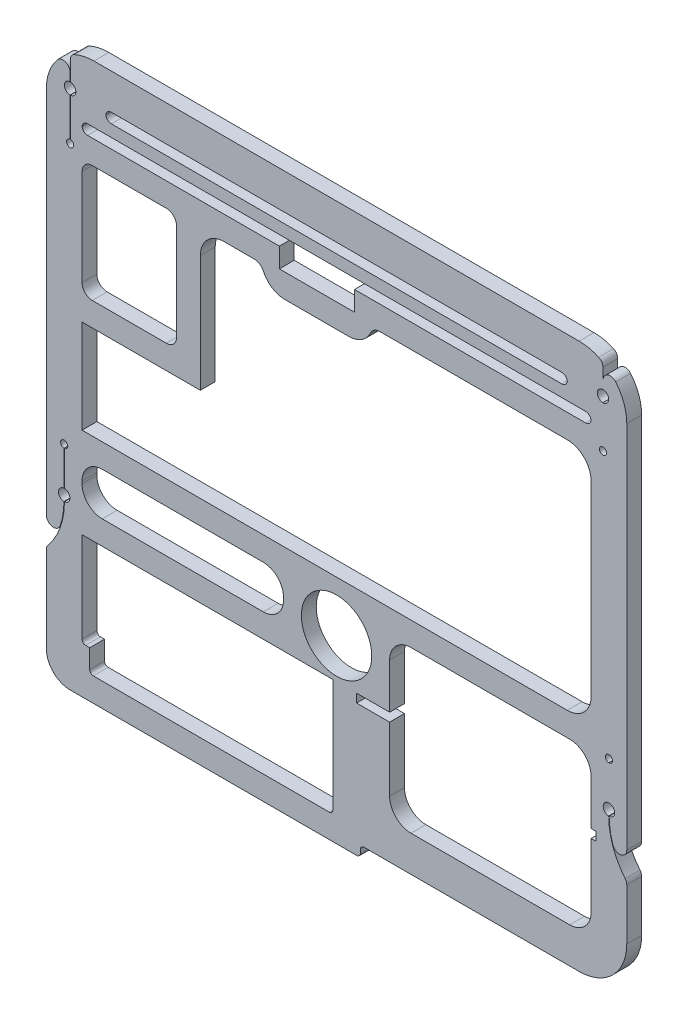
SolidWorks part; units mm, degrees
ref_plane "Front Plane" through (0, 0, 0) normal (0, 0, 1) x (1, 0, 0)
ref_plane "Top Plane" through (0, 0, 0) normal (0, 1, 0) x (1, 0, 0)
ref_plane "Right Plane" through (0, 0, 0) normal (1, 0, 0) x (0, 0, -1)
sketch "Sketch1" plane through (0, 0, 0) normal (0, 0, 1) x (1, 0, 0)
  line L0 (63.9883, 88.3985) -> (63.9883, 84.5885) construction
  line L1 (48.2422, 30.1083) -> (110.2188, 30.1083)
  line L2 (48.2422, 30.1083) -> (48.2422, 88.3985)
  line L3 (48.2422, 88.3985) -> (110.2188, 88.3985)
  line L4 (110.2188, 30.1083) -> (110.2188, 88.3985)
  line L5 (106.4088, 84.5885) -> (52.0522, 84.5885)
  line L6 (106.4088, 84.5885) -> (106.4088, 33.9183)
  line L7 (106.4088, 33.9183) -> (52.0522, 33.9183)
  line L8 (52.0522, 84.5885) -> (52.0522, 33.9183)
  line L9 (63.9883, 86.4935) -> (18.0707, 86.4935) construction
  line L10 (52.0522, 41.2855) -> (48.2422, 41.2855) construction
  line L11 (50.1472, 41.2855) -> (50.1472, 25.8577) construction
  line L12 (13.5248, 33.9183) -> (13.5248, 30.1083) construction
  line L13 (13.5248, 32.0133) -> (21.1598, 32.0133) construction
  line L14 (110.2188, 38.1916) -> (106.4088, 38.1916) construction
  line L15 (108.3138, 38.1916) -> (108.3138, 22.3321) construction
  line L16 (106.4088, 54.6152) -> (106.4088, 79.5085) construction
  line L17 (52.0522, 74.5555) -> (52.0522, 54.6152) construction
  line L22 (79.0876, 86.4935) -> (79.6338, 86.4935) construction
  line L23 (96.5564, 32.0133) -> (96.0102, 32.0133) construction
  dimension "D1" = 3.81
  dimension "D2" = 3.81
extrude "Boss-Extrude1" add sketch "Sketch1" along normal blind 1.5875
sketch "Sketch2" plane through (0, 0, 0) normal (0, 0, -1) x (-1, 0, 0)
  line L0 (-106.4088, 33.9183) -> (-106.4088, 84.5885) construction
  line L1 (-106.4088, 53.6273) -> (-52.0522, 53.6273)
  line L2 (-106.4088, 53.6273) -> (-106.4088, 51.0873)
  line L3 (-106.4088, 51.0873) -> (-52.0522, 51.0873)
  line L4 (-52.0522, 53.6273) -> (-52.0522, 51.0873)
  line L5 (-52.0522, 84.5885) -> (-52.0522, 33.9183) construction
  line L6 (-57.1852, 53.6273) -> (-94.8852, 53.6273) construction
  line L8 (-99.4108, 81.1849) -> (-61.0568, 81.1849) construction
  line L9 (-80.5132, 79.0767) -> (-73.7568, 79.0767) construction
  line L10 (-80.5132, 81.1849) -> (-80.5132, 79.0767) construction
  line L11 (-106.4088, 81.1849) -> (-81.1482, 81.1849)
  line L12 (-106.4088, 81.1849) -> (-106.4088, 78.6449)
  line L13 (-106.4088, 78.6449) -> (-83.0532, 78.6449)
  line L14 (-52.0522, 81.1849) -> (-52.0522, 78.6449)
  line L15 (-106.4088, 83.5217) -> (-52.0522, 83.5217)
  line L16 (-106.4088, 83.5217) -> (-106.4088, 82.2517)
  line L17 (-106.4088, 82.2517) -> (-52.0522, 82.2517)
  line L18 (-52.0522, 83.5217) -> (-52.0522, 82.2517)
  line L19 (-73.7568, 79.0767) -> (-73.7568, 81.1849) construction
  line L20 (-80.5132, 81.1849) -> (-80.5132, 79.0767) construction
  line L21 (-73.7568, 79.0767) -> (-73.7568, 81.1849) construction
  line L22 (-81.1482, 79.0767) -> (-81.1482, 81.1849)
  line L23 (-73.1218, 79.0767) -> (-81.1482, 79.0767)
  line L24 (-73.1218, 79.0767) -> (-73.1218, 81.1849)
  line L25 (-83.0532, 78.6449) -> (-83.0532, 76.5367)
  line L26 (-83.0532, 76.5367) -> (-71.2168, 76.5367)
  line L27 (-71.2168, 76.5367) -> (-71.2168, 78.6449)
  line L28 (-71.2168, 78.6449) -> (-52.0522, 78.6449)
  line L29 (-73.1218, 81.1849) -> (-52.0522, 81.1849)
  line L30 (-81.1482, 71.7401) -> (-80.5132, 71.7401) construction
  line L31 (-57.9086, 84.5885) -> (-57.9086, 83.5217) construction
  line L32 (-73.7568, 71.6584) -> (-73.1218, 71.6584) construction
  line L33 (-106.4088, 84.5885) -> (-52.0522, 84.5885) construction
  line L35 (-57.9086, 82.2517) -> (-57.9086, 81.1849) construction
  dimension "D1" = 2.54
  dimension "D2" = 1.905
  dimension "D3" = 2.54
  dimension "D4" = 1.905
  dimension "D5" = 1.27
  dimension "D6" = 0.635
extrude "Boss-Extrude2" add sketch "Sketch2" against normal up to surface (1.5875 mm away) up to face at (79.2305, 59.2534, 1.5875)
sketch "Sketch3" plane through (0, 0, 0) normal (0, 0, -1) x (-1, 0, 0)
  line L1 (-60.4352, 63.6273) -> (-52.0522, 63.6273) construction
  line L12 (-64.6852, 63.6273) -> (-13.0532, 63.6273)
  line L13 (-13.0532, 63.6273) -> (-52.0522, 63.6273)
  line L14 (-52.0522, 78.6449) -> (-52.0522, 53.6273) construction
  line L15 (-52.0522, 63.6273) -> (-52.0522, 66.1673)
  line L16 (-52.0522, 66.1673) -> (-62.1452, 66.1673)
  line L17 (-62.1452, 66.1673) -> (-62.1452, 78.6449)
  line L18 (-71.2168, 78.6449) -> (-52.0522, 78.6449) construction
  line L19 (-62.1452, 78.6449) -> (-64.6852, 78.6449)
  line L20 (-64.6852, 78.6449) -> (-64.6852, 63.6273)
  line M27 (-71.2168, 78.6449) -> (-52.0522, 78.6449)
  line M28 (-52.0522, 78.6449) -> (-52.0522, 53.6273)
  dimension "D3" = 2.54
  dimension "D4" = 2.54
extrude "Boss-Extrude3" add sketch "Sketch3" against normal up to surface (1.5875 mm away) contours L20 L12 L13 L16 L17 M27 M28 region at (64.4889, 71.1361, 0) up to face at (79.2305, 84.0551, 1.5875)
sketch "Sketch14" plane through (0, 0, 1.5875) normal (0, 0, 1) x (1, 0, 0)
  line L0 (78.3192, 43.964) -> (52.5602, 43.964) construction
  line L1 (84.8947, 43.964) -> (84.8947, 48.5473) construction
  line L2 (84.8947, 33.9183) -> (84.8947, 51.0873)
  line L4 (78.3192, 43.964) -> (52.0522, 43.964)
  line L5 (52.0522, 51.0873) -> (52.0522, 33.9183) construction
  line L6 (52.0522, 51.0873) -> (106.4088, 51.0873) construction
  line L7 (52.0522, 33.9183) -> (106.4088, 33.9183) construction
  line L9 (78.3192, 43.964) -> (78.3192, 33.9183)
  line L10 (78.3192, 33.9183) -> (84.8947, 33.9183)
  line L11 (52.0522, 51.0873) -> (84.8947, 51.0873)
  line L12 (52.0522, 51.0873) -> (52.0522, 43.964)
extrude "Boss-Extrude9" add sketch "Sketch14" against normal up to surface (1.5875 mm away) up to face at (75.4832, 70.2163, 0)
sketch "Sketch5" plane through (0, 0, 0) normal (0, 0, -1) x (-1, 0, 0)
  line L1 (-52.8684, 31.5053) -> (-78.8272, 31.5053) construction
  line L2 (-52.8684, 31.5053) -> (-52.8684, 43.964) construction
  line L6 (-52.8684, 43.964) -> (-78.8272, 43.964) construction
  line L7 (-78.8272, 31.5053) -> (-78.8272, 43.964) construction
  line L8 (-52.8684, 31.5053) -> (-78.8272, 31.5053)
  line L9 (-52.8684, 31.5053) -> (-52.8684, 43.964)
  line L10 (-52.8684, 43.964) -> (-78.8272, 43.964)
  line L11 (-78.8272, 31.5053) -> (-78.8272, 43.964)
  circle A1 centre (-79.2305, 48.2171) radius 3.7592 construction
  circle A2 centre (-79.2305, 48.2171) radius 3.7592
extrude "Cut-Extrude1" cut sketch "Sketch5" against normal up to surface (1.5875 mm away) up to face at (65.1857, 38.9412, 1.5875)
fillet "Fillet1" radius 5.08 3 edges at (110.2188, 30.1083, 0.7937) (48.2422, 88.3985, 0.7937) (110.2188, 88.3985, 0.7937)
fillet "Fillet2" radius 2.54 5 edges at (64.6852, 78.6449, 0.7937) (71.2168, 76.5367, 0.7937) (106.4088, 78.6449, 0.7937) (106.4088, 53.6273, 0.7937) (83.0532, 76.5367, 0.7937)
fillet "Fillet3" radius 1.0922 6 edges at (52.0522, 66.1673, 0.7937) (62.1452, 66.1673, 0.7937) (52.0522, 78.6449, 0.7937) (62.1452, 78.6449, 0.7937) (71.2168, 78.6449, 0.7937) (83.0532, 78.6449, 0.7937)
fillet "Fillet4" radius 0.5842 4 edges at (52.0522, 81.1849, 0.7937) (52.0522, 82.2517, 0.7938) (106.4088, 82.2517, 0.7937) (106.4088, 81.1849, 0.7937)
sketch "Sketch6" plane through (0, 0, 0) normal (0, 0, -1) x (-1, 0, 0)
  line L0 (-53.6852, 62.1273) -> (-53.6852, 55.1273) construction
  line L1 (-53.6852, 62.1273) -> (-53.6852, 55.1273)
  line L2 (-55.1852, 63.6273) -> (-53.6852, 62.1273) construction
  line L3 (-55.1852, 63.6273) -> (-53.6852, 62.1273)
  line L4 (-55.1852, 63.6273) -> (-55.1852, 53.6273)
  line L6 (-57.1852, 55.1273) -> (-57.1852, 53.6273)
  line L7 (-57.1852, 53.6273) -> (-55.1852, 53.6273)
  line L8 (-55.1852, 53.6273) -> (-53.6852, 55.1273)
  line L9 (-53.6852, 55.1273) -> (-57.1852, 55.1273)
  line L12 (-55.1852, 53.6273) -> (-53.6852, 55.1273)
  circle A0 centre (-107.6788, 84.5885) radius 0.6096 construction
  circle A1 centre (-50.7822, 84.5885) radius 0.6096 construction
  circle A2 centre (-108.3138, 46.6777) radius 0.6096 construction
  circle A3 centre (-50.1472, 46.6777) radius 0.6096 construction
  circle A4 centre (-107.6788, 84.5885) radius 0.6096
  circle A5 centre (-50.7822, 84.5885) radius 0.6096
  circle A6 centre (-108.3138, 46.6777) radius 0.6096
  circle A7 centre (-50.1472, 46.6777) radius 0.6096
  dimension "D1" = 0
extrude "Cut-Extrude2" cut sketch "Sketch6" against normal up to surface (1.5875 mm away) up to face at (75.4713, 48.2171, 1.5875)
sketch "Sketch9" plane through (0, 0, 1.5875) normal (0, 0, 1) x (1, 0, 0)
  line L4 (106.945, 43.964) -> (81.3672, 43.964)
  line L5 (81.3672, 43.964) -> (81.3672, 43.0496)
  line L6 (81.3672, 43.0496) -> (106.945, 43.0496)
  line L7 (106.945, 43.0496) -> (106.945, 43.964)
  line L8 (106.945, 43.964) -> (81.3672, 43.964)
  line L9 (81.3672, 43.964) -> (81.3672, 43.0496)
  line L10 (81.3672, 43.0496) -> (106.945, 43.0496)
  line L11 (106.945, 43.0496) -> (106.945, 43.964)
  dimension "D1" = 0
extrude "Cut-Extrude3" cut sketch "Sketch9" against normal up to surface (1.5875 mm away) up to face at (49.5376, 46.6777, 0)
sketch "Sketch11" plane through (0, 0, 1.5875) normal (0, 0, 1) x (1, 0, 0)
  line L0 (52.8684, 31.5053) -> (78.8272, 31.5053) construction
  line L1 (48.2422, 30.1083) -> (81.7705, 30.1083)
  line L2 (48.2422, 30.1083) -> (48.2422, 28.9653)
  line L3 (48.2422, 28.9653) -> (81.7705, 28.9653)
  line L4 (81.7705, 30.1083) -> (81.7705, 28.9653)
  line L5 (79.2305, 51.9763) -> (79.2305, -22.2214) construction
  circle A0 centre (79.2305, 48.2171) radius 3.7592 construction
  dimension "D1" = 2.54
  dimension "D2" = 2.54
extrude "Boss-Extrude6" add sketch "Sketch11" against normal up to surface (1.5875 mm away) up to face at (95.1532, 43.1722, 0)
fillet "Fillet7" radius 2.54 1 edges at (48.2422, 28.9653, 0.7937)
fillet "Fillet8" radius 0.381 2 edges at (81.7705, 28.9653, 0.7937) (81.7705, 30.1083, 0.7937)
sketch "Sketch12" plane through (0, 0, 1.5875) normal (0, 0, 1) x (1, 0, 0)
  line L0 (52.0522, 84.5885) -> (52.0522, 83.5217) construction
  line L1 (52.0522, 84.5885) -> (54.5922, 84.5885)
  line L2 (52.0522, 84.5885) -> (52.0522, 83.5217)
  line L3 (52.0522, 83.5217) -> (54.5922, 83.5217)
  line L4 (54.5922, 84.5885) -> (54.5922, 83.5217)
  line L5 (106.4088, 84.5885) -> (52.0522, 84.5885) construction
  line L6 (106.4088, 83.5217) -> (52.0522, 83.5217) construction
  line L8 (106.4088, 84.5885) -> (103.8688, 84.5885)
  line L9 (106.4088, 84.5885) -> (106.4088, 83.5217)
  line L10 (106.4088, 83.5217) -> (103.8688, 83.5217)
  line L11 (103.8688, 84.5885) -> (103.8688, 83.5217)
  dimension "D1" = 2.54
extrude "Boss-Extrude7" add sketch "Sketch12" against normal up to surface (1.5875 mm away) up to face at (95.1532, 43.1722, 0)
fillet "Fillet11" radius 0.5842 4 edges at (103.8688, 83.5217, 0.7937) (103.8688, 84.5885, 0.7937) (54.5922, 83.5217, 0.7937) (54.5922, 84.5885, 0.7937)
sketch "Sketch13" plane through (0, 0, 1.5875) normal (0, 0, 1) x (1, 0, 0)
  line L0 (50.7695, 86.0858) -> (50.7695, 85.198) construction
  line L1 (50.7949, 85.198) -> (50.7949, 87.2592) construction
  line L2 (50.7695, 83.9791) -> (50.7695, 79.8893) construction
  line L3 (50.7949, 79.8893) -> (50.7949, 83.9791) construction
  line L4 (107.6661, 85.198) -> (107.6661, 87.2592) construction
  line L5 (107.6915, 83.9791) -> (107.6915, 79.8893) construction
  line L6 (107.6661, 79.8893) -> (107.6661, 83.9791) construction
  line L7 (108.3265, 50.9963) -> (108.3265, 47.2872) construction
  line L8 (108.3011, 50.9963) -> (108.3011, 47.2872) construction
  line L9 (50.1345, 50.9963) -> (50.1345, 47.2872) construction
  line L10 (50.1599, 50.9963) -> (50.1599, 47.2872) construction
  line L11 (50.7695, 86.0858) -> (50.7695, 85.198)
  line L12 (50.7949, 85.198) -> (50.7949, 87.2592)
  line L13 (50.7695, 83.9791) -> (50.7695, 79.8893)
  line L14 (50.7949, 79.8893) -> (50.7949, 83.9791)
  line L15 (107.6661, 85.198) -> (107.6661, 87.2592)
  line L16 (107.6915, 83.9791) -> (107.6915, 79.8893)
  line L17 (107.6661, 79.8893) -> (107.6661, 83.9791)
  line L18 (108.3265, 50.9963) -> (108.3265, 47.2872)
  line L19 (108.3011, 50.9963) -> (108.3011, 47.2872)
  line L20 (50.1345, 50.9963) -> (50.1345, 47.2872)
  line L21 (50.1599, 50.9963) -> (50.1599, 47.2872)
  line L22 (48.2422, 83.3185) -> (48.2422, 31.5053) construction
  line L23 (110.2188, 35.1883) -> (110.2188, 83.3185) construction
  line L24 (48.2422, 43.8754) -> (48.2422, 40.6699)
  line L25 (110.2188, 40.6699) -> (110.2188, 43.8754)
  line L26 (107.6915, 83.9791) -> (107.6915, 79.8893)
  line L27 (107.6915, 86.0858) -> (107.6915, 85.198) construction
  line L28 (107.6915, 86.0858) -> (107.6915, 85.198)
  arc A0 (107.6661, 83.9791) -> (107.6915, 83.9791) centre (107.6788, 84.5885) ccw
  arc A1 (50.7695, 86.0858) -> (49.4225, 86.5742) centre (50.0075, 86.0858) ccw construction
  arc A2 (51.2454, 87.9546) -> (50.7949, 87.2592) centre (51.5569, 87.2592) ccw construction
  arc A3 (50.7695, 79.8893) -> (50.7949, 79.8893) centre (50.7822, 79.5085) ccw construction
  arc A4 (107.6661, 87.2592) -> (107.2156, 87.9546) centre (106.9041, 87.2592) ccw construction
  arc A5 (109.0384, 86.5742) -> (107.6915, 86.0858) centre (108.4535, 86.0858) ccw construction
  arc A6 (107.6661, 79.8893) -> (107.6915, 79.8893) centre (107.6788, 79.5085) ccw construction
  arc A7 (108.3265, 50.9963) -> (108.3011, 50.9963) centre (108.3138, 51.3771) ccw construction
  arc A8 (108.3392, 46.0687) -> (108.7338, 43.6346) centre (116.0396, 46.0681) ccw construction
  arc A9 (108.7338, 43.6346) -> (110.2188, 43.8754) centre (109.4568, 43.8754) ccw construction
  arc A10 (108.2884, 46.0687) -> (110.046, 41.153) centre (116.0396, 46.0681) ccw construction
  arc A11 (110.2188, 40.6699) -> (110.046, 41.153) centre (109.4568, 40.6699) ccw construction
  arc A12 (48.2422, 43.8754) -> (49.7271, 43.6346) centre (49.0042, 43.8754) ccw construction
  arc A13 (50.1599, 50.9963) -> (50.1345, 50.9963) centre (50.1472, 51.3771) ccw construction
  arc A14 (48.415, 41.153) -> (50.1726, 46.0687) centre (42.4214, 46.0681) ccw construction
  arc A15 (49.7271, 43.6346) -> (50.1218, 46.0687) centre (42.4214, 46.0681) ccw construction
  arc A16 (48.415, 41.153) -> (48.2422, 40.6699) centre (49.0042, 40.6699) ccw construction
  arc A17 (50.7695, 83.9791) -> (50.7949, 83.9791) centre (50.7822, 84.5885) ccw
  arc A18 (50.7695, 86.0858) -> (49.4225, 86.5742) centre (50.0075, 86.0858) ccw
  arc A19 (51.2454, 87.9546) -> (50.7949, 87.2592) centre (51.5569, 87.2592) ccw
  arc A20 (50.7695, 79.8893) -> (50.7949, 79.8893) centre (50.7822, 79.5085) ccw
  arc A21 (107.6661, 87.2592) -> (107.2156, 87.9546) centre (106.9041, 87.2592) ccw
  arc A22 (109.0384, 86.5742) -> (107.6915, 86.0858) centre (108.4535, 86.0858) ccw
  arc A23 (107.6661, 79.8893) -> (107.6915, 79.8893) centre (107.6788, 79.5085) ccw
  arc A24 (108.3265, 50.9963) -> (108.3011, 50.9963) centre (108.3138, 51.3771) ccw
  arc A25 (108.3392, 46.0687) -> (108.7338, 43.6346) centre (116.0396, 46.0681) ccw
  arc A26 (108.7338, 43.6346) -> (110.2188, 43.8754) centre (109.4568, 43.8754) ccw
  arc A27 (108.2884, 46.0687) -> (110.046, 41.153) centre (116.0396, 46.0681) ccw
  arc A28 (110.2188, 40.6699) -> (110.046, 41.153) centre (109.4568, 40.6699) ccw
  arc A29 (48.2422, 43.8754) -> (49.7271, 43.6346) centre (49.0042, 43.8754) ccw
  arc A30 (50.1599, 50.9963) -> (50.1345, 50.9963) centre (50.1472, 51.3771) ccw
  arc A31 (48.415, 41.153) -> (50.1726, 46.0687) centre (42.4214, 46.0681) ccw
  arc A32 (49.7271, 43.6346) -> (50.1218, 46.0687) centre (42.4214, 46.0681) ccw
  arc A33 (48.415, 41.153) -> (48.2422, 40.6699) centre (49.0042, 40.6699) ccw
  circle A34 centre (50.7822, 84.5885) radius 0.6096 construction
  circle A35 centre (107.6788, 84.5885) radius 0.6096 construction
  circle A36 centre (108.3138, 46.6777) radius 0.6096 construction
  circle A37 centre (50.1472, 46.6777) radius 0.6096 construction
  arc A38 (53.3222, 88.3985) -> (48.2422, 83.3185) centre (53.3222, 83.3185) ccw construction
  arc A39 (110.2188, 83.3185) -> (105.1388, 88.3985) centre (105.1388, 83.3185) ccw construction
  arc A40 (50.7949, 85.198) -> (50.7695, 85.198) centre (50.7822, 84.5885) ccw
  arc A41 (107.6661, 83.9791) -> (107.6915, 83.9791) centre (107.6788, 84.5885) ccw
  arc A42 (108.3265, 47.2872) -> (108.3011, 47.2872) centre (108.3138, 46.6777) ccw
  arc A43 (50.1218, 46.0687) -> (50.1726, 46.0687) centre (50.1472, 46.6777) ccw
  arc A44 (51.2454, 87.9546) -> (49.4225, 86.5742) centre (53.3222, 83.3185) ccw
  arc A45 (109.0384, 86.5742) -> (107.2156, 87.9546) centre (105.1388, 83.3185) ccw
  arc A46 (50.1599, 47.2872) -> (50.1345, 47.2872) centre (50.1472, 46.6777) ccw
  arc A47 (108.2884, 46.0687) -> (108.3392, 46.0687) centre (108.3138, 46.6777) ccw
  arc A48 (107.6915, 85.198) -> (107.6661, 85.198) centre (107.6788, 84.5885) ccw
extrude "Cut-Extrude4" cut sketch "Sketch13" against normal through all contours A48 L28 A22 A45 A21 L15 | L17 A23 L16 A0 | A47 A27 A28 L25 A26 A25 | A42 L18 A24 L19 | A43 A32 A29 L24 A33 A31 | A46 L21 A30 L20 | A19 A44 A18 L11 A40 L12 | L13 A20 L14 A17 region at (50.4642, 87.0334, 1.5875) region at (50.7822, 79.9586, 1.5875) region at (107.9968, 87.0334, 1.5875) region at (107.6788, 79.9586, 1.5875) region at (108.3138, 50.9944, 1.5875) region at (50.1472, 50.9944, 1.5875) region at (48.8136, 42.5993, 1.5875) region at (109.6474, 42.5993, 1.5875)
fillet "Fillet12" radius 2.286 4 edges at (106.4088, 33.9183, 0.7937) (106.4088, 51.0873, 0.7937) (84.8947, 33.9183, 0.7937) (84.8947, 51.0873, 0.7937)
fillet "Fillet13" radius 0.381 3 edges at (52.0522, 33.9183, 0.7937) (52.8684, 31.5053, 0.7937) (78.8272, 31.5053, 0.7937)
sketch "Sketch15" plane through (0, 0, 1.5875) normal (0, 0, 1) x (1, 0, 0)
  line L0 (73.5663, 48.9283) -> (73.5663, 48.663) construction
  line L1 (71.4073, 46.504) -> (54.2112, 46.504) construction
  line L2 (52.0522, 48.9283) -> (52.0522, 48.663) construction
  line L3 (54.2112, 51.0873) -> (71.4073, 51.0873) construction
  line L4 (73.5663, 48.9283) -> (73.5663, 48.663)
  line L5 (71.4073, 46.504) -> (54.2112, 46.504)
  line L6 (52.0522, 48.9283) -> (52.0522, 48.663)
  line L7 (54.2112, 51.0873) -> (71.4073, 51.0873)
  arc A0 (73.5663, 48.9283) -> (71.4073, 51.0873) centre (71.4073, 48.9283) ccw construction
  arc A1 (71.4073, 46.504) -> (73.5663, 48.663) centre (71.4073, 48.663) ccw construction
  arc A2 (52.0522, 48.663) -> (54.2112, 46.504) centre (54.2112, 48.663) ccw construction
  arc A3 (54.2112, 51.0873) -> (52.0522, 48.9283) centre (54.2112, 48.9283) ccw construction
  arc A4 (73.5663, 48.9283) -> (71.4073, 51.0873) centre (71.4073, 48.9283) ccw
  arc A5 (71.4073, 46.504) -> (73.5663, 48.663) centre (71.4073, 48.663) ccw
  arc A6 (52.0522, 48.663) -> (54.2112, 46.504) centre (54.2112, 48.663) ccw
  arc A7 (54.2112, 51.0873) -> (52.0522, 48.9283) centre (54.2112, 48.9283) ccw
extrude "Cut-Extrude5" cut sketch "Sketch15" against normal through all
